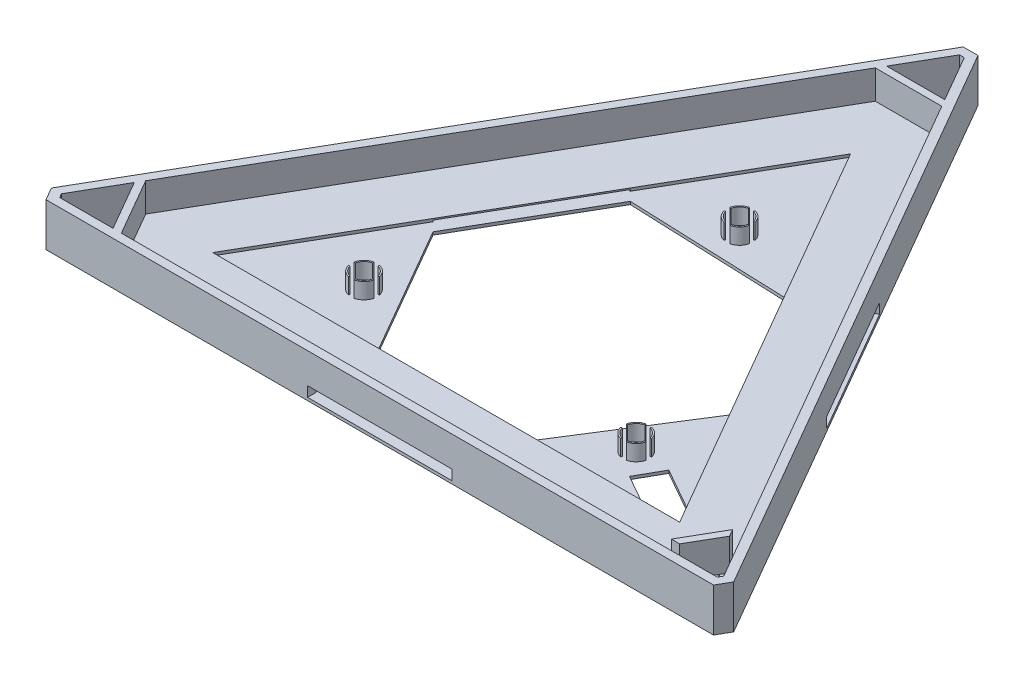
SolidWorks part; units mm, degrees
ref_plane "Front Plane" through (0, 0, 0) normal (0, 0, 1) x (1, 0, 0)
ref_plane "Top Plane" through (0, 0, 0) normal (0, 1, 0) x (1, 0, 0)
ref_plane "Right Plane" through (0, 0, 0) normal (1, 0, 0) x (0, 0, -1)
sketch "Sketch1" plane through (0, 0, 0) normal (0, 1, 0) x (1, 0, 0)
  line L0 (351.2729, 67.6655) -> (468.273, -134.9846)
  line L1 (347.2728, 67.6655) -> (347.2728, 65.1655) construction
  line L2 (409.773, -33.6595) -> (407.6079, -34.9095) construction
  line L3 (468.273, -134.9846) -> (464.2732, -141.9124)
  line L4 (230.2733, -141.9124) -> (464.2732, -141.9124)
  line L5 (230.2733, -141.9124) -> (226.2727, -134.9842)
  line L6 (226.2727, -134.9842) -> (343.2728, 67.6655)
  line L7 (353.4142, 63.9567) -> (351.2491, 62.7067) construction
  line L8 (347.2733, -141.9124) -> (347.2733, -139.4124) construction
  line L9 (231.7167, -139.4124) -> (462.8299, -139.4124)
  line L10 (284.7727, -33.6594) -> (286.9378, -34.9094) construction
  line L11 (344.7161, 65.1655) -> (349.8295, 65.1655)
  line L12 (465.3862, -134.9846) -> (349.8295, 65.1655)
  line L13 (466.2731, -138.4485) -> (464.1081, -137.1985) construction
  line L14 (462.8299, -139.4124) -> (465.3862, -134.9846)
  line L15 (229.1594, -134.9842) -> (344.7161, 65.1655)
  line L16 (229.1594, -134.9842) -> (231.7167, -139.4124)
  line L17 (286.9378, -34.9094) -> (287.3708, -35.1594) construction
  line L18 (230.438, -137.1983) -> (230.871, -136.9483) construction
  line L19 (232.0053, -138.9123) -> (229.7368, -134.9842)
  line L20 (343.2728, 67.6655) -> (351.2729, 67.6655)
  line L21 (345.0048, 64.6655) -> (229.7368, -134.9842)
  line L22 (349.5409, 64.6655) -> (345.0048, 64.6655)
  line L23 (249.0568, -126.4468) -> (246.8918, -127.697) construction
  line L24 (407.6079, -34.9095) -> (407.1749, -35.1595) construction
  line L26 (233.4463, -136.4089) -> (251.9226, -136.4093)
  line L27 (464.8089, -134.9846) -> (462.5412, -138.9123)
  line L28 (462.5412, -138.9123) -> (232.0053, -138.9123)
  line L29 (251.9226, -136.4093) -> (241.8609, -118.9847)
  line L30 (241.8609, -118.9847) -> (232.6236, -134.9842)
  line L31 (232.6236, -134.9842) -> (233.4463, -136.4089)
  line L33 (287.3708, -35.1594) -> (289.5359, -36.4094) construction
  line L34 (254.8093, -136.4089) -> (243.3042, -116.4848)
  line L35 (335.7675, 43.666) -> (243.3042, -116.4848)
  line L36 (358.7782, 43.666) -> (335.7675, 43.666)
  line L38 (289.5359, -36.4094) -> (306.8564, -46.4094) construction
  line L41 (461.939, -134.9846) -> (461.1164, -136.4093)
  line L42 (347.2688, -136.4172) -> (347.2688, -116.4172) construction
  line L43 (442.6021, -136.4093) -> (452.6999, -118.9847)
  line L44 (245.2636, -119.878) -> (249.0568, -126.4468) construction
  line L45 (452.6999, -118.9847) -> (461.939, -134.9846)
  line L48 (461.1164, -136.4093) -> (442.6021, -136.4093)
  line L49 (405.0134, -36.4027) -> (387.6936, -46.404) construction
  line L50 (306.8564, -46.4094) -> (466.2731, -138.4485) construction
  line L51 (357.3348, 46.166) -> (337.2109, 46.166)
  line L52 (337.2109, 46.166) -> (346.4484, 62.1659)
  line L53 (346.4484, 62.1659) -> (348.0966, 62.164)
  line L54 (348.0966, 62.164) -> (357.3348, 46.166)
  line L55 (228.273, -138.4483) -> (387.6936, -46.404) construction
  line L56 (347.2688, -116.4172) -> (347.2728, 43.666) construction
  line L57 (266.4391, -116.428) -> (428.1137, -116.4172)
  line L58 (347.2736, 23.6092) -> (428.1137, -116.4172)
  line L59 (266.4391, -116.428) -> (347.2736, 23.6092)
  line L60 (439.7283, -136.4254) -> (439.7283, -132.9254) construction
  line L61 (451.2487, -116.4715) -> (448.6507, -117.9717) construction
  line L62 (452.6999, -118.9847) -> (358.7782, 43.666)
  line L63 (442.6021, -136.4093) -> (254.8093, -136.4089)
  line L64 (441.749, -132.9254) -> (444.621, -132.9254)
  line L65 (448.6507, -117.9717) -> (450.9647, -121.979) construction
  line L66 (449.5167, -119.4714) -> (450.9647, -121.979)
  line L67 (441.749, -132.9254) -> (449.5167, -119.4714)
  line L68 (450.9647, -121.979) -> (444.621, -132.9254)
  point P13 (407.6079, -34.9095)
  point P20 (464.1081, -137.1985)
  point P23 (347.2733, -139.4124)
  point P25 (347.2732, -141.9124)
  point P27 (347.2728, 65.1655)
  point P31 (286.9378, -34.9094)
  point P37 (287.3708, -35.1594)
  point P39 (230.871, -136.9483)
  point P41 (347.2728, 64.6655)
  point P45 (407.1749, -35.1595)
  point P50 (246.8918, -127.697)
  point P56 (289.5359, -36.4094)
  point P58 (249.0568, -126.4468)
  point P60 (347.2728, 43.666)
  point P62 (345.0048, -136.4089)
  point P64 (445.4885, -126.4485)
  point P71 (447.651, -127.697)
  point P77 (347.2728, 46.166)
  point P84 (347.2688, -116.4172)
  point P87 (387.6936, -46.404)
  point P89 (306.8564, -46.4094)
  point P100 (405.0134, -36.4027)
  dimension "D1" = 2.5
  dimension "D2" = 2.5
  dimension "D3" = 2.5
  dimension "D4" = 2.5
  dimension "D5" = 2.5
  dimension "D6" = 2.5
  dimension "D7" = 0.5
  dimension "D8" = 0.5
  dimension "D9" = 0.5
  dimension "D10" = 2.5
  dimension "D11" = 2.5
  dimension "D12" = 20
  dimension "D13" = 20
  dimension "D14" = 20
  dimension "D15" = 3.5
  dimension "D16" = 3
extrude "Boss-Extrude1" add sketch "Sketch1" along normal blind 1 contours L36 L35 L34 L57 L59 L58 region at (251.4484, 0, 125.0658)
extrude "Boss-Extrude2" add sketch "Sketch1<9>" along normal blind 11 contours L28 L27 L22 L21 L19 L31 L30 L29 L26 L34 L35 L36 L41 L48 L43 L45 L53 L54 L51 L52 | L68 L64 L67 L66 region at (230.7087, 0, 137.042)
sketch "Sketch1<9>" plane through (0, 0, 0) normal (0, 1, 0) x (1, 0, 0) same geometry as "Sketch1"
extrude "Boss-Extrude3" add sketch "Sketch1<10>" along normal blind 5 and the other way blind 3 contours L28 L27 L22 L21 L19 L31 L30 L29 L26 L34 L35 L36 L41 L48 L43 L45 L53 L54 L51 L52 region at (230.7087, 0, 137.042)
sketch "Sketch1<10>" plane through (0, 0, 0) normal (0, 1, 0) x (1, 0, 0) same geometry as "Sketch1"
sketch "Sketch3" plane through (290.5896, 0, -167.772) normal (0.866, 0, -0.5) x (-0.5, 0, -0.866)
  line L1 (-261.593, -6.5) -> (-211.593, -6.5)
  line L2 (-261.593, -6.5) -> (-261.593, 0.5)
  line L3 (-261.593, 0.5) -> (-211.593, 0.5)
  line L4 (-211.593, -6.5) -> (-211.593, 0.5)
  line L5 (-261.593, -6.5) -> (-211.593, 0.5) construction
  line L6 (-261.593, 0.5) -> (-211.593, -6.5) construction
  point P0 (-236.593, -3)
  dimension "D1" = 50
  dimension "D2" = 7
extrude "Cut-Extrude3" cut sketch "Sketch3" against normal blind 25
sketch "Sketch5" plane through (0, 0, 139.4124) normal (0, 0, 1) x (1, 0, 0)
  line L0 (231.7167, -3) -> (462.8299, -3) construction
  line L1 (322.2733, -6.5) -> (372.2733, -6.5)
  line L2 (322.2733, -6.5) -> (322.2733, 0.5)
  line L3 (322.2733, 0.5) -> (372.2733, 0.5)
  line L4 (372.2733, -6.5) -> (372.2733, 0.5)
  line L5 (322.2733, -6.5) -> (372.2733, 0.5) construction
  line L6 (322.2733, 0.5) -> (372.2733, -6.5) construction
  point P0 (347.2733, -3)
  dimension "D1" = 50
  dimension "D2" = 7
extrude "Cut-Extrude4" cut sketch "Sketch5" against normal blind 25
sketch "Sketch6" plane through (230.3194, 0, 132.9752) normal (-0.866, 0, -0.5) x (-0.5, 0, 0.866)
  line L0 (2.3199, -3) -> (-228.7932, -3) construction
  line L1 (-138.2367, -6.5) -> (-88.2367, -6.5)
  line L2 (-138.2367, -6.5) -> (-138.2367, 0.5)
  line L3 (-138.2367, 0.5) -> (-88.2367, 0.5)
  line L4 (-88.2367, -6.5) -> (-88.2367, 0.5)
  line L5 (-138.2367, -6.5) -> (-88.2367, 0.5) construction
  line L6 (-138.2367, 0.5) -> (-88.2367, -6.5) construction
  point P0 (-113.2367, -3)
  dimension "D1" = 50
  dimension "D2" = 7
extrude "Cut-Extrude5" cut sketch "Sketch6" against normal blind 25
sketch "Sketch8" plane through (0, -3, 0) normal (0, -1, 0) x (1, 0, 0)
  line L1 (349.8295, -65.1655) -> (465.3862, 134.9846)
  line L2 (465.3862, 134.9846) -> (462.8299, 139.4124)
  line L6 (462.8299, 139.4124) -> (231.7167, 139.4124)
  line L7 (450.147, 123.2807) -> (452.6999, 118.9847)
  line L9 (452.6999, 118.9847) -> (461.939, 134.9846)
  line L12 (461.939, 134.9846) -> (461.1164, 136.4093)
  line L17 (461.1164, 136.4093) -> (442.6021, 136.4093)
  line L19 (322.2733, 116.4243) -> (294.3582, 68.0611)
  line L20 (294.3582, 68.0611) -> (319.3545, 24.7577)
  line L21 (319.3545, 24.7577) -> (376.4737, 26.9694)
  line L22 (376.4737, 26.9694) -> (401.4727, 70.2712)
  line L23 (401.4727, 70.2712) -> (372.2733, 116.4209)
  line L24 (372.2733, 116.4209) -> (322.2733, 116.4243)
  line L25 (386.873, 93.3461) -> (395.3235, 98.6928) construction
  line L30 (308.3157, 92.2427) -> (299.6549, 97.2417) construction
  line L31 (347.9141, 25.8635) -> (348.3013, 15.8635) construction
  line L34 (401.698, 107.3846) -> (445.2267, 131.9864)
  line L35 (450.147, 123.2807) -> (406.6183, 98.6788)
  line L36 (401.698, 107.3846) -> (406.6183, 98.6788)
  line L37 (231.7167, 139.4124) -> (229.1594, 134.9842)
  line L39 (233.4463, 136.4089) -> (251.9226, 136.4093)
  line L40 (251.9226, 136.4093) -> (241.8609, 118.9847)
  line L41 (241.8609, 118.9847) -> (232.6236, 134.9842)
  line L42 (232.6236, 134.9842) -> (233.4463, 136.4089)
  line L43 (349.8295, -65.1655) -> (344.7161, -65.1655)
  line L44 (344.7161, -65.1655) -> (229.1594, 134.9842)
  line L45 (337.2109, -46.166) -> (357.3348, -46.166)
  line L46 (357.3348, -46.166) -> (348.0966, -62.164)
  line L47 (348.0966, -62.164) -> (346.4484, -62.1659)
  line L48 (346.4484, -62.1659) -> (337.2109, -46.166)
  line L49 (442.6021, 136.4093) -> (445.2267, 131.9864)
  circle A0 centre (395.3235, 98.6928) radius 1.5
  circle A1 centre (348.3013, 15.8635) radius 1.5
  circle A2 centre (299.6549, 97.2417) radius 1.5
  dimension "D6" = 3
  dimension "D7" = 3
  dimension "D8" = 3
  dimension "D1" = 10
  dimension "D2" = 50
  dimension "D3" = 10
  dimension "D4" = 10
  dimension "D5" = 10
extrude "Boss-Extrude5" add sketch "Sketch8" along normal blind 1
sketch "Sketch12" plane through (0, -3, 0) normal (0, 1, 0) x (1, 0, 0)
  line L0 (348.3013, -11.8635) -> (348.3013, -11.3635) construction
  line L1 (348.3013, -11.3635) -> (349.2951, -11.4746) construction
  line L2 (349.2951, -11.4746) -> (349.1847, -11.9623)
  line L3 (348.3013, -11.3635) -> (347.3075, -11.4746) construction
  line L4 (347.3075, -11.4746) -> (347.4179, -11.9623)
  line L5 (352.3013, -15.8635) -> (352.8013, -15.8635) construction
  line L6 (344.3013, -15.8635) -> (343.8013, -15.8635) construction
  line L7 (348.3013, -19.8635) -> (348.3013, -20.3635) construction
  line L8 (352.8013, -15.8635) -> (352.6902, -14.8697) construction
  line L9 (352.8013, -15.8635) -> (352.6902, -16.8573) construction
  line L10 (343.8013, -15.8635) -> (343.9124, -14.8697) construction
  line L11 (343.8013, -15.8635) -> (343.9124, -16.8573) construction
  line L12 (348.3013, -20.3635) -> (349.2951, -20.2524) construction
  line L13 (348.3013, -20.3635) -> (347.3075, -20.2524) construction
  line L14 (343.9124, -14.8697) -> (348.3013, -15.8635) construction
  line L15 (348.3013, -15.8635) -> (352.6902, -14.8697) construction
  line L16 (343.9124, -16.8573) -> (348.3013, -15.8635) construction
  line L17 (348.3013, -15.8635) -> (352.6902, -16.8573) construction
  line L18 (347.3075, -20.2524) -> (348.3013, -15.8635) construction
  line L19 (348.3013, -15.8635) -> (349.2951, -20.2524) construction
  line L20 (343.9124, -14.8697) -> (344.4001, -14.9801)
  line L21 (343.9124, -16.8573) -> (344.4001, -16.7469)
  line L22 (347.3075, -20.2524) -> (347.4179, -19.7648)
  line L23 (349.2951, -20.2524) -> (349.1847, -19.7648)
  line L24 (352.6902, -14.8697) -> (352.2025, -14.9801)
  line L25 (352.6902, -16.8573) -> (352.2025, -16.7469)
  line L26 (395.3235, -94.1928) -> (395.3235, -98.6928) construction
  line L27 (395.3235, -98.6928) -> (390.8235, -98.6928) construction
  line L28 (390.8235, -98.6928) -> (390.9347, -97.699) construction
  line L29 (399.8235, -98.6928) -> (395.3235, -98.6928) construction
  line L30 (395.3235, -98.6928) -> (395.3235, -103.1928) construction
  line L31 (395.3235, -103.1928) -> (396.3173, -103.0817) construction
  line L32 (395.3235, -94.1928) -> (396.3173, -94.3039) construction
  line L33 (395.3235, -94.1928) -> (394.3297, -94.3039) construction
  line L34 (399.7124, -97.699) -> (399.8235, -98.6928) construction
  line L35 (399.8235, -98.6928) -> (399.7124, -99.6866) construction
  line L36 (390.9347, -99.6866) -> (390.8235, -98.6928) construction
  line L37 (394.3297, -103.0817) -> (395.3235, -103.1928) construction
  line L38 (394.3297, -94.3039) -> (395.3235, -98.6928) construction
  line L39 (395.3235, -98.6928) -> (396.3173, -94.3039) construction
  line L40 (390.9347, -99.6866) -> (395.3235, -98.6928) construction
  line L41 (395.3235, -98.6928) -> (390.9347, -97.699) construction
  line L42 (399.7124, -97.699) -> (395.3235, -98.6928) construction
  line L43 (395.3235, -98.6928) -> (399.7124, -99.6866) construction
  line L44 (394.3297, -103.0817) -> (395.3235, -98.6928) construction
  line L45 (395.3235, -98.6928) -> (396.3173, -103.0817) construction
  line L46 (394.3297, -94.3039) -> (394.4402, -94.7916)
  line L47 (396.3173, -94.3039) -> (396.2069, -94.7916)
  line L48 (399.7124, -97.699) -> (399.2248, -97.8094)
  line L49 (399.7124, -99.6866) -> (399.2248, -99.5762)
  line L50 (396.3173, -103.0817) -> (396.2069, -102.5941)
  line L51 (394.3297, -103.0817) -> (394.4402, -102.5941)
  line L52 (390.9347, -99.6866) -> (391.4223, -99.5762)
  line L53 (390.9347, -97.699) -> (391.4248, -97.7985)
  line L54 (299.6549, -92.7417) -> (299.6549, -97.2417) construction
  line L55 (299.6549, -97.2417) -> (304.1549, -97.2417) construction
  line L56 (299.6549, -101.7417) -> (299.6549, -97.2417) construction
  line L57 (299.6549, -97.2417) -> (295.1549, -97.2417) construction
  line L58 (299.6549, -97.2417) -> (298.6611, -92.8528) construction
  line L59 (298.6611, -92.8528) -> (299.6549, -92.7417) construction
  line L60 (299.6549, -92.7417) -> (300.6487, -92.8528) construction
  line L61 (300.6487, -92.8528) -> (299.6549, -97.2417) construction
  line L62 (299.6549, -97.2417) -> (304.0438, -96.2479) construction
  line L63 (304.0438, -96.2479) -> (304.1549, -97.2417) construction
  line L64 (304.1549, -97.2417) -> (304.0438, -98.2355) construction
  line L65 (304.0438, -98.2355) -> (299.6549, -97.2417) construction
  line L66 (299.6549, -97.2417) -> (300.6487, -101.6306) construction
  line L67 (300.6487, -101.6306) -> (299.6549, -101.7417) construction
  line L68 (299.6549, -101.7417) -> (298.6611, -101.6306) construction
  line L69 (298.6611, -101.6306) -> (299.6549, -97.2417) construction
  line L70 (299.6549, -97.2417) -> (295.266, -98.2355) construction
  line L71 (295.266, -98.2355) -> (295.1549, -97.2417) construction
  line L72 (295.1549, -97.2417) -> (295.266, -96.2479) construction
  line L73 (295.266, -96.2479) -> (299.6549, -97.2417) construction
  line L74 (295.266, -96.2479) -> (295.7537, -96.3583)
  line L75 (295.266, -98.2355) -> (295.7537, -98.1251)
  line L76 (298.6611, -101.6306) -> (298.7715, -101.1429)
  line L77 (300.6487, -101.6306) -> (300.5383, -101.1429)
  line L78 (304.0438, -98.2355) -> (303.5561, -98.1251)
  line L79 (304.0438, -96.2479) -> (303.5561, -96.3583)
  line L80 (300.6487, -92.8528) -> (300.5383, -93.3404)
  line L81 (298.6611, -92.8528) -> (298.7715, -93.3404)
  circle A0 centre (348.3013, -15.8635) radius 4.5
  circle A1 centre (395.3235, -98.6928) radius 4.5
  circle A2 centre (299.6549, -97.2417) radius 4.5
  circle A3 centre (348.3013, -15.8635) radius 4
  circle A4 centre (395.3235, -98.6928) radius 4
  circle A5 centre (299.6549, -97.2417) radius 4
  dimension "D1" = 9
  dimension "D2" = 9
  dimension "D3" = 9
  dimension "D4" = 8
  dimension "D5" = 8
  dimension "D6" = 8
  dimension "D7" = 1
  dimension "D8" = 1
  dimension "D9" = 1
  dimension "D10" = 1
  dimension "D11" = 1
  dimension "D12" = 1
  dimension "D13" = 1
  dimension "D14" = 1
  dimension "D15" = 1
  dimension "D16" = 1
  dimension "D17" = 1
  dimension "D18" = 1
  dimension "D19" = 1
  dimension "D20" = 1
  dimension "D21" = 1
  dimension "D22" = 1
  dimension "D23" = 1
  dimension "D24" = 1
  dimension "D25" = 1
  dimension "D26" = 1
  dimension "D27" = 1
  dimension "D28" = 1
  dimension "D29" = 1
  dimension "D30" = 1
extrude "Boss-Extrude10" add sketch "Sketch12" along normal blind 5.5 contours A3 L4 A0 L20 | A3 L24 A0 L2 | A3 L23 A0 L25 | A3 L21 A0 L22 | A4 L46 A1 L53 | A4 L48 A1 L47 | A4 L50 A1 L49 | A4 L52 A1 L51 | A5 L81 A2 L74 | A5 L79 A2 L80 | A5 L77 A2 L78 | A5 L75 A2 L76 region at (351.1537, -3, 13.0111) region at (345.4489, -3, 13.0111) region at (351.1537, -3, 18.7159) region at (345.4489, -3, 18.7159) region at (392.4726, -3, 95.8382) region at (398.1759, -3, 95.8404) region at (392.4712, -3, 101.5452) region at (398.1759, -3, 101.5452) region at (296.8025, -3, 94.3893) region at (296.8025, -3, 100.0941) region at (302.5073, -3, 94.3893) region at (302.5073, -3, 100.0941)
